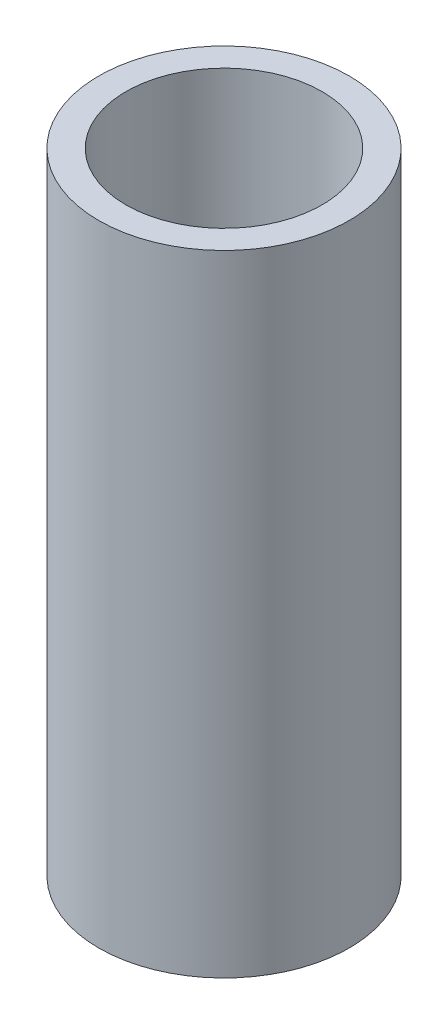
SolidWorks part; units mm, degrees
ref_plane "Front Plane" through (0, 0, 0) normal (0, 0, 1) x (1, 0, 0)
ref_plane "Top Plane" through (0, 0, 0) normal (0, 1, 0) x (1, 0, 0)
ref_plane "Right Plane" through (0, 0, 0) normal (1, 0, 0) x (0, 0, -1)
sketch "Sketch1" plane through (0, 0, 0) normal (0, 1, 0) x (1, 0, 0)
  circle A0 centre (0, 0) radius 22.5
  dimension "SLEEVE_OD" = 45
extrude "Boss-Extrude1" add sketch "Sketch1" along normal blind 113.2007
sketch "Sketch2" plane through (0, 0, 0) normal (0, 1, 0) x (1, 0, 0)
  circle A0 centre (0, 0) radius 17.6315
  dimension "BORE_D" = 35.263
extrude "Cut-Extrude1" cut sketch "Sketch2" along normal through all
chamfer "Chamfer1" distance 3.4956 angle 42.632 rebuild error yes
